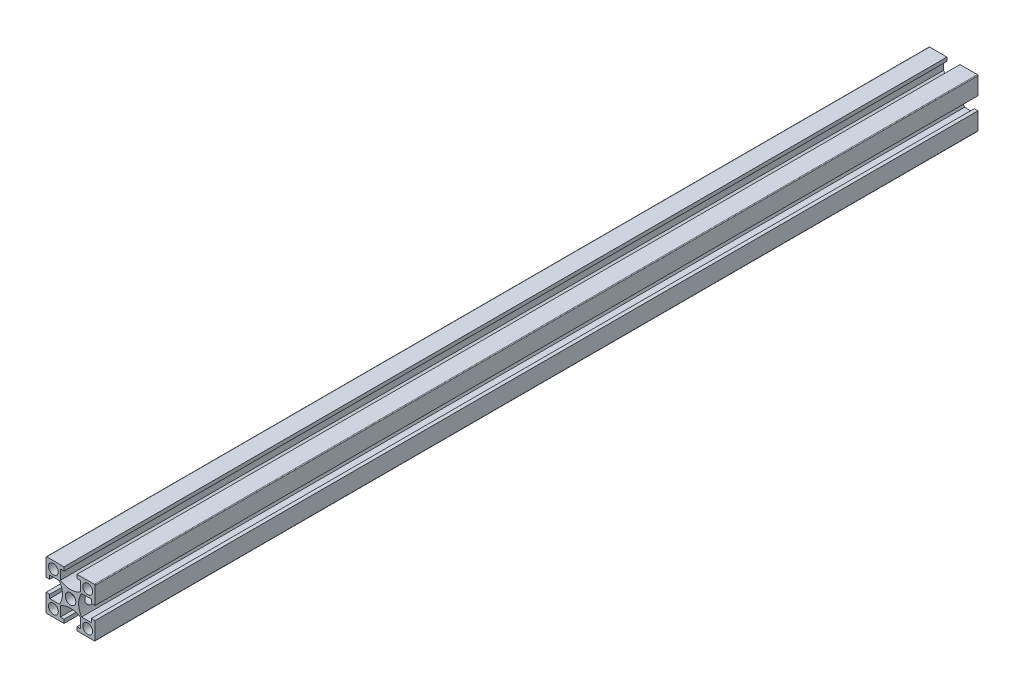
SolidWorks part; units mm, degrees
material "3.0255 (EN-AW 1350A)"
ref_plane "정면" through (0, 0, 0) normal (0, 0, 1) x (1, 0, 0)
ref_plane "윗면" through (0, 0, 0) normal (0, 1, 0) x (1, 0, 0)
ref_plane "우측면" through (0, 0, 0) normal (1, 0, 0) x (0, 0, -1)
sketch "스케치1" plane through (0, 0, 0) normal (0, 0, 1) x (1, 0, 0)
  line L0 (0, 32.0265) -> (0, -31.6588) construction
  line L1 (-10, 10) -> (-10, -10)
  line L2 (-10, 10) -> (10, 10)
  line L3 (-10, 2.65) -> (-8.5, 2.65)
  line L4 (13.6618, 0) -> (-11.6993, 0) construction
  line L5 (-8.5, 2.65) -> (-8.5, 4.15)
  line L6 (-8.5, 4.15) -> (-4.5032, 4.15)
  line L7 (-10, -2.65) -> (-8.5, -2.65)
  line L8 (-8.5, -2.65) -> (-8.5, -4.15)
  line L9 (-8.5, -4.15) -> (-4.5032, -4.15)
  line L10 (-10, -10) -> (10, -10)
  line L11 (10, 10) -> (10, -10)
  circle A0 centre (-7, 7) radius 2
  circle A1 centre (-7, -7) radius 2
  arc A2 (-4.5032, 4.15) -> (-4.5032, -4.15) centre (-11.0587, 0) cw
  circle A3 centre (0, 0) radius 2.15
  circle A4 centre (7, 7) radius 2
  circle A5 centre (7, -7) radius 2
  point P21 (-10, 0)
  point P23 (-3.3, 0)
  point P31 (0, -10)
  point P32 (0, 10)
  dimension "D3" = 4
  dimension "D9" = 6.7
  dimension "D10" = 4.3
  dimension "D11" = 7.7587
  dimension "D1" = 20
  dimension "D2" = 20
  dimension "D4" = 14
  dimension "D5" = 14
  dimension "D6" = 5.3
  dimension "D7" = 8.3
  dimension "D8" = 1.5
extrude "보스-돌출1" add sketch "스케치1" along normal blind 360 contours A0 | A4 | A3 | A5 | A1 | A2 L6 L5 L3 L1 L7 L8 L9 | L2 L11 L10 L1 region at (-6.6069, 0, 0) region at (-7, 7, 0) region at (-7, -7, 0) region at (0, 0, 0) region at (7, 7, 0) region at (7, -7, 0)
extrude "컷-돌출1" cut sketch "스케치1<3>" along normal up to next contours A2 L6 L5 L3 L1 L7 L8 L9 region at (-6.6069, 0, 0)
sketch "스케치1<3>" plane through (0, 0, 0) normal (0, 0, 1) x (1, 0, 0) same geometry as "스케치1"
pattern_circular "원형 패턴1" count 4 over 360 about axis through (0, 0, 360) along (0, 0, -1) of "컷-돌출1" reverse direction yes
fillet "필렛1" radius 0.3 4 edges at (10, -10, 180) (-10, -10, 180) (-10, 10, 180) (10, 10, 180)
sketch "스케치2" plane through (0, 0, 0) normal (1, 0, 0) x (0, 0, -1)
  line L0 (0, -2.65) -> (0, -9.7) construction
  line L1 (-360, 4.15) -> (-360, -4.15) construction
  circle A0 centre (-5, 0) radius 2.5
  circle A1 centre (-355, 0) radius 2.5
  dimension "D1" = 5
  dimension "D4" = 5
  dimension "D2" = 5
  dimension "D3" = 5
extrude "컷-돌출2" cut sketch "스케치2" against normal through all both and the other way through all contours A0 | A1
sketch "스케치3" plane through (10, 0, 0) normal (1, 0, 0) x (0, 0, -1)
  line L0 (-33.65, 9.7) -> (-33.65, -9.7) construction
  line L1 (0, 9.7) -> (-360, 9.7) construction
  line L2 (-360, -9.7) -> (0, -9.7) construction
  line L3 (-166.62, 9.7) -> (-166.62, -9.7) construction
  line L4 (-326.1, 9.7) -> (-326.1, -9.7) construction
  line L5 (0, -2.65) -> (0, -9.7) construction
  line L6 (-346.1, 9.7) -> (-346.1, -9.7) construction
  line L7 (-186.62, 9.7) -> (-186.62, -9.7) construction
  line L8 (-53.65, 9.7) -> (-53.65, -9.7) construction
  circle A0 centre (-64.65, 0) radius 2.5
  circle A1 centre (-155.62, 0) radius 2.5
  circle A2 centre (-197.62, 0) radius 2.5
  circle A3 centre (-315.1, 0) radius 2.5
  dimension "D7" = 11
  dimension "D8" = 11
  dimension "D1" = 33.65
  dimension "D2" = 166.62
  dimension "D3" = 326.1
  dimension "D10" = 11
  dimension "D5" = 20
  dimension "D4" = 20
  dimension "D6" = 20
extrude "컷-돌출3" [suppressed] cut sketch "스케치3" against normal through all
sketch "스케치4" plane through (10, 0, 0) normal (1, 0, 0) x (0, 0, -1)
  line L0 (-326.35, 9.7) -> (-326.35, -9.7) construction
  line L1 (0, 9.7) -> (-360, 9.7) construction
  line L2 (-360, -9.7) -> (0, -9.7) construction
  line L3 (-193.38, 9.7) -> (-193.38, -9.7) construction
  line L4 (-33.9, 9.7) -> (-33.9, -9.7) construction
  line L5 (-360, 9.7) -> (-360, 2.65) construction
  line L6 (-306.35, 9.7) -> (-306.35, -9.7) construction
  line L7 (-173.38, 9.7) -> (-173.38, -9.7) construction
  line L8 (-13.9, 9.7) -> (-13.9, -9.7) construction
  line L9 (0, -2.65) -> (0, -9.7) construction
  circle A4 centre (-316.35, 0) radius 2.5
  circle A5 centre (-183.38, 0) radius 2.5
  circle A6 centre (-23.9, 0) radius 2.5
  dimension "D7" = 10
  dimension "D1" = 33.65
  dimension "D2" = 166.62
  dimension "D3" = 326.1
  dimension "D4" = 20
  dimension "D5" = 20
  dimension "D6" = 20
extrude "컷-돌출4" cut sketch "스케치4" against normal through all
